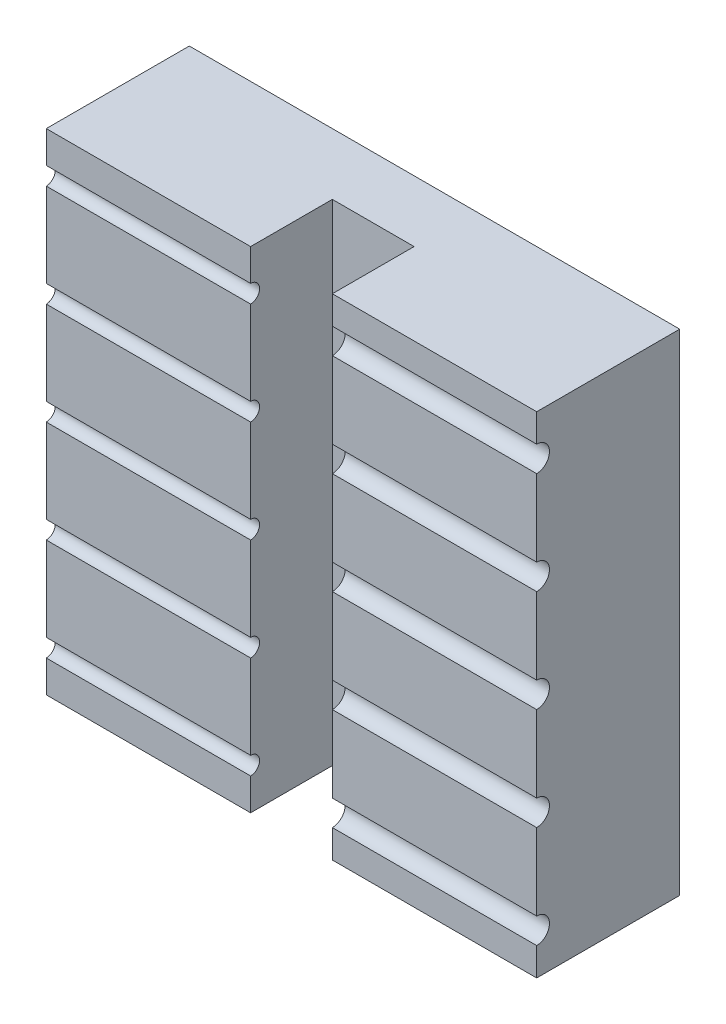
SolidWorks part; units mm, degrees
ref_plane "Front Plane" through (0, 0, 0) normal (0, 0, 1) x (1, 0, 0)
ref_plane "Top Plane" through (0, 0, 0) normal (0, 1, 0) x (1, 0, 0)
ref_plane "Right Plane" through (0, 0, 0) normal (1, 0, 0) x (0, 0, -1)
sketch "Sketch1" plane through (0, 0, 0) normal (0, 0, 1) x (1, 0, 0)
  line L1 (-24, -24) -> (24, -24)
  line L2 (-24, -24) -> (-24, 24)
  line L3 (-24, 24) -> (24, 24)
  line L4 (24, -24) -> (24, 24)
  line L5 (-24, -24) -> (24, 24) construction
  line L6 (-24, 24) -> (24, -24) construction
  line L7 (-24, -24) -> (-4, -24)
  line L8 (-24, -24) -> (-24, 24)
  line L9 (-24, 24) -> (-4, 24)
  line L10 (-4, -24) -> (-4, 24)
  line L11 (24, -24) -> (4, -24)
  line L12 (24, -24) -> (24, 24)
  line L13 (24, 24) -> (4, 24)
  line L14 (4, -24) -> (4, 24)
  point P0 (0, 0)
  dimension "D1" = 48
  dimension "D2" = 20
  dimension "D5" = 20
extrude "Boss-Extrude1" add sketch "Sketch1" along normal blind 6 contours L1 L10 L3 L2 | L1 L14 L3 L10 | L14 L1 L4 L3 region at (-14, 0, 0) region at (0, 0, 0) region at (14, 0, 0)
extrude "Boss-Extrude2" add sketch "Sketch1<3>" along normal blind 14 contours L1 L10 L3 L2 | L14 L1 L4 L3 region at (-14, 0, 0) region at (14, 0, 0)
sketch "Sketch1<3>" plane through (0, 0, 0) normal (0, 0, 1) x (1, 0, 0) same geometry as "Sketch1"
sketch "Sketch2" plane through (-24, 0, 0) normal (-1, 0, 0) x (0, 0, 1)
  line L0 (14, -24) -> (14, 24) construction
  circle A0 centre (14, 0) radius 0.875
  circle A1 centre (14, 10) radius 0.875
  circle A2 centre (14, 20) radius 0.875
  circle A3 centre (14, 0) radius 0.875
  circle A4 centre (14, 10) radius 0.875
  circle A5 centre (14, -10) radius 0.875
  circle A6 centre (14, 0) radius 0.875
  circle A7 centre (14, -10) radius 0.875
  circle A8 centre (14, -20) radius 0.875
  dimension "D1" = 1.75
  dimension "D2" = 3
extrude "Cut-Extrude1" cut sketch "Sketch2" against normal blind 25 contours A8 | A5 | A0 | A1 | A2
sketch "Sketch3" plane through (24, 0, 0) normal (1, 0, 0) x (0, 0, -1)
  line L0 (-14, -24) -> (-14, 24) construction
  circle A0 centre (-14, 0) radius 1.25
  circle A1 centre (-14, -10) radius 1.25
  circle A2 centre (-14, -20) radius 1.25
  circle A3 centre (-14, 0) radius 1.25
  circle A4 centre (-14, -10) radius 1.25
  circle A5 centre (-14, 10) radius 1.25
  circle A6 centre (-14, 0) radius 1.25
  circle A7 centre (-14, 10) radius 1.25
  circle A8 centre (-14, 20) radius 1.25
  dimension "D1" = 2.5
  dimension "D2" = 3
extrude "Cut-Extrude2" cut sketch "Sketch3" against normal blind 25 contours A2 | A0 | A1 | A5 | A8
